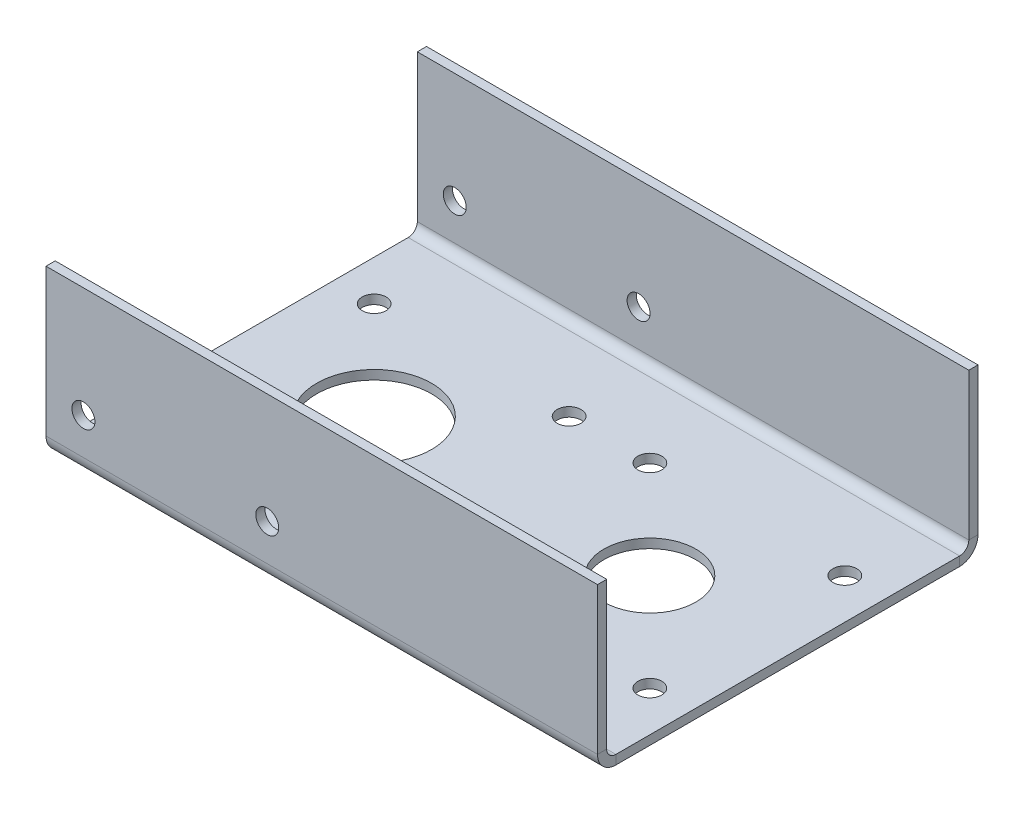
SolidWorks part; units mm, degrees
note: The reader was unsure of these and kept them because the rebuilt part matched: flange length of "Edge-Flange1".
ref_plane "Front Plane" through (0, 0, 0) normal (0, 0, 1) x (1, 0, 0)
ref_plane "Top Plane" through (0, 0, 0) normal (0, 1, 0) x (1, 0, 0)
ref_plane "Right Plane" through (0, 0, 0) normal (1, 0, 0) x (0, 0, -1)
sketch "Sketch1" plane through (0, 0, 0) normal (0, 1, 0) x (1, 0, 0)
  line L0 (-38.1, 25.019) -> (0, -25.019) construction
  line L1 (-38.1, 25.019) -> (38.1, 25.019)
  line L2 (-38.1, 25.019) -> (-38.1, -25.019)
  line L3 (-38.1, -25.019) -> (38.1, -25.019)
  line L4 (38.1, 25.019) -> (38.1, -25.019)
  line L5 (-38.1, 25.019) -> (38.1, -25.019) construction
  circle A0 centre (-19.05, 0) radius 7.9375
  point P0 (-19.05, 0)
  point P8 (0, 0)
  point P9 (-19.05, 0)
  dimension "D3" = 15.875
  dimension "D1" = 76.2
  dimension "D2" = 50.038
base flange "Base-Flange1" sketch "Sketch1" thickness 1.27 reverse thickness direction no parameters "D1"=1.27
edge flange "Edge-Flange1" sketch "Sketch8" flange angle 90 flange length 22.86 flange position material outside bend radius 1.27 thickness 1.27 relief rectangular parameters "D6"=10
sketch "Sketch8" plane through (0, 0, 25.019) normal (0, 0, 1) x (1, 0, 0)
  line L0 (-38.1, 0) -> (38.1, 0) construction
  line L1 (-38.1, 0) -> (38.1, 0)
  line L2 (-38.1, 0) -> (-38.1, 21.59)
  line L3 (-38.1, 21.59) -> (38.1, 21.59)
  line L4 (38.1, 21.59) -> (38.1, 0)
  dimension "D1" = 21.59
bend "EdgeBend1" bend radius 1.27 bend angle 90 parameters "D5"=1
mirror "Mirror1" about plane through (0, 0, 0) normal (0, 0, 1) of "Edge-Flange1"
bend "MirrorBend1" bend radius 1.27 bend angle 90 parameters "D5"=2
sketch "Sketch9" plane through (0, 0, 0) normal (0, 1, 0) x (1, 0, 0)
  line L2 (-19.05, 0) -> (-42.2675, 0) construction
  line L3 (-19.05, 0) -> (-32.5204, 13.4704) construction
  circle A3 centre (-32.5204, 13.4704) radius 1.651
  circle A5 centre (-19.05, 0) radius 19.05 construction
  dimension "D4" = 3.302
  dimension "D5" = 38.1
  dimension "D6" = 45
extrude "Cut-Extrude3" cut sketch "Sketch9" against normal through all contours A3 normal cut yes
pattern_circular "CirPattern2" count 4 over 360 about axis through (-19.05, 0, 0) along (0, 1, 0) of "Cut-Extrude3"
sketch "Sketch11" plane through (0, 0, 0) normal (0, 1, 0) x (1, 0, 0)
  line L0 (-19.05, 0) -> (19.05, 0) construction
  line L1 (19.05, 0) -> (5.5796, 13.4704) construction
  circle A0 centre (19.05, 0) radius 6.35
  circle A1 centre (19.05, 0) radius 19.05 construction
  circle A2 centre (5.5796, 13.4704) radius 1.651
  dimension "D1" = 12.7
  dimension "D2" = 38.1
  dimension "D4" = 3.302
  dimension "D3" = 38.1
  dimension "D5" = 45
extrude "Cut-Extrude4" cut sketch "Sketch11" against normal blind 2.54 normal cut yes
pattern_circular "CirPattern3" count 4 over 360 about axis through (19.05, 0, 0) along (0, 1, 0) of "Cut-Extrude4"
sketch "Sketch10" plane through (0, 0, -26.289) normal (0, 0, -1) x (-1, 0, 0)
  line L0 (-38.1, 6.35) -> (38.1, 6.35) construction
  line L1 (-38.1, 1.27) -> (-38.1, 21.59) construction
  line L2 (38.1, 21.59) -> (38.1, 1.27) construction
  line L5 (38.1, 1.27) -> (-38.1, 1.27) construction
  circle A0 centre (7.5286, 6.35) radius 1.5875
  circle A1 centre (32.9286, 6.35) radius 1.5875
  dimension "D1" = 3.175
  dimension "D2" = 25.4
  dimension "D4" = 5.1714
  dimension "D3" = 5.08
extrude "Cut-Extrude2" cut sketch "Sketch10" against normal through all both and the other way through all normal cut yes
sketch "Bend-Lines1" [suppressed] plane through (0, 0, 0) normal (0, 1, 0) x (1, 0, 0)
sketch "Bounding-Box1" [suppressed] plane through (0, 0, 0) normal (0, 1, 0) x (1, 0, 0)
sheet metal parameters "Sheet-Metal1" thickness 1.27 parameters "D1"=1.27
flat pattern "Flat-Pattern1" [suppressed]
sketch "Bend-Lines2" plane through (0, 0, 0) normal (0, 1, 0) x (1, 0, 0)
sketch3d "Bounding-Box2" [suppressed]
  line L0 (18.0975, 22.225, 0) -> (18.0975, -22.225, 0) construction
  line L1 (-18.0975, 22.225, 0) -> (-18.0975, -22.225, 0) construction
  line L2 (18.0975, 22.225, 0) -> (-18.0975, 22.225, 0) construction
  line L3 (18.0975, -22.225, 0) -> (-18.0975, -22.225, 0) construction
sheet metal parameters "Sheet-Metal2" thickness 1.27 parameters "D1"=1.27
flat pattern "Flat-Pattern1"
sketch "Bend-Lines2" plane through (0, 0, 0) normal (0, 1, 0) x (1, 0, 0)
  line L0 (-18.0975, -22.4512) -> (18.0975, -22.4512) construction
  line L1 (-18.0975, -22.4512) -> (18.0975, -22.4512) construction
sketch3d "Bounding-Box2" [suppressed]
  line L0 (-18.0975, 22.225, 0) -> (-18.0975, -34.1074, 0) construction
  line L1 (18.0975, 22.225, 0) -> (18.0975, -34.1074, 0) construction
  line L2 (-18.0975, 22.225, 0) -> (18.0975, 22.225, 0) construction
  line L3 (-18.0975, -34.1074, 0) -> (18.0975, -34.1074, 0) construction
bend of the flat pattern "Flatten-<EdgeBend1>1"
sheet metal parameters "Sheet-Metal3" thickness 1.27 parameters "D1"=1.27
flat pattern "Flat-Pattern1"
sketch "Bend-Lines2" plane through (0, 0, 0) normal (0, 1, 0) x (1, 0, 0)
  line L0 (-38.1, -25.2452) -> (38.1, -25.2452) construction
  line L1 (-38.1, -25.2452) -> (38.1, -25.2452) construction
  line L2 (38.1, 25.2452) -> (-38.1, 25.2452) construction
  line L3 (38.1, 25.2452) -> (-38.1, 25.2452) construction
sketch3d "Bounding-Box2" [suppressed]
  line L0 (38.1, -36.9014, 0) -> (-38.1, -36.9014, 0) construction
  line L1 (38.1, 36.9014, 0) -> (-38.1, 36.9014, 0) construction
  line L2 (38.1, -36.9014, 0) -> (38.1, 36.9014, 0) construction
  line L3 (-38.1, -36.9014, 0) -> (-38.1, 36.9014, 0) construction
bend of the flat pattern "Flatten-<EdgeBend1>1"
bend of the flat pattern "Flatten-<MirrorBend1>1"
sheet metal parameters "Sheet-Metal6" thickness 1.27 parameters "D1"=1.27
flat pattern "Flat-Pattern1"
sketch "Bend-Lines2" plane through (0, 0, 0) normal (0, 1, 0) x (1, 0, 0)
  line L0 (-38.1, -25.2452) -> (38.1, -25.2452) construction
  line L1 (-38.1, -25.2452) -> (38.1, -25.2452) construction
  line L2 (38.1, 25.2452) -> (-38.1, 25.2452) construction
  line L3 (38.1, 25.2452) -> (-38.1, 25.2452) construction
sketch3d "Bounding-Box2" [suppressed]
  line L0 (-38.1, 47.0614, 0) -> (-38.1, -47.0614, 0) construction
  line L1 (38.1, 47.0614, 0) -> (38.1, -47.0614, 0) construction
  line L2 (-38.1, 47.0614, 0) -> (38.1, 47.0614, 0) construction
  line L3 (-38.1, -47.0614, 0) -> (38.1, -47.0614, 0) construction
bend of the flat pattern "Flatten-<EdgeBend1>1"
bend of the flat pattern "Flatten-<MirrorBend1>1"
sheet metal parameters "Sheet-Metal9" thickness 1.27 parameters "D1"=1.27
flat pattern "Flat-Pattern1"
sketch "Bend-Lines2" plane through (0, 0, 0) normal (0, 1, 0) x (1, 0, 0)
  line L0 (-38.1, -25.2452) -> (38.1, -25.2452) construction
  line L1 (-38.1, -25.2452) -> (38.1, -25.2452) construction
  line L2 (38.1, 25.2452) -> (-38.1, 25.2452) construction
  line L3 (38.1, 25.2452) -> (-38.1, 25.2452) construction
sketch3d "Bounding-Box2" [suppressed]
  line L0 (38.1, -36.9014, 0) -> (-38.1, -36.9014, 0) construction
  line L1 (38.1, 36.9014, 0) -> (-38.1, 36.9014, 0) construction
  line L2 (38.1, -36.9014, 0) -> (38.1, 36.9014, 0) construction
  line L3 (-38.1, -36.9014, 0) -> (-38.1, 36.9014, 0) construction
bend of the flat pattern "Flatten-<EdgeBend1>1"
bend of the flat pattern "Flatten-<MirrorBend1>1"
sheet metal parameters "Sheet-Metal10" thickness 1.27 parameters "D1"=1.27
flat pattern "Flat-Pattern1"
sketch "Bend-Lines2" plane through (0, 0, 0) normal (0, 1, 0) x (1, 0, 0)
  line L0 (-38.1, -25.2452) -> (38.1, -25.2452) construction
  line L1 (-38.1, -25.2452) -> (38.1, -25.2452) construction
  line L2 (38.1, 25.2452) -> (-38.1, 25.2452) construction
  line L3 (38.1, 25.2452) -> (-38.1, 25.2452) construction
sketch3d "Bounding-Box2" [suppressed]
  line L0 (38.1, -36.9014, 0) -> (-38.1, -36.9014, 0) construction
  line L1 (38.1, 36.9014, 0) -> (-38.1, 36.9014, 0) construction
  line L2 (38.1, -36.9014, 0) -> (38.1, 36.9014, 0) construction
  line L3 (-38.1, -36.9014, 0) -> (-38.1, 36.9014, 0) construction
bend of the flat pattern "Flatten-<EdgeBend1>1"
bend of the flat pattern "Flatten-<MirrorBend1>1"
sheet metal parameters "Sheet-Metal11" thickness 1.27 parameters "D1"=1.27
flat pattern "Flat-Pattern1"
sketch "Bend-Lines2" plane through (0, 0, 0) normal (0, 1, 0) x (1, 0, 0)
  line L0 (-38.1, -25.2452) -> (38.1, -25.2452) construction
  line L1 (-38.1, -25.2452) -> (38.1, -25.2452) construction
  line L2 (38.1, 25.2452) -> (-38.1, 25.2452) construction
  line L3 (38.1, 25.2452) -> (-38.1, 25.2452) construction
sketch3d "Bounding-Box2" [suppressed]
  line L0 (38.1, -36.9014, 0) -> (-38.1, -36.9014, 0) construction
  line L1 (38.1, 36.9014, 0) -> (-38.1, 36.9014, 0) construction
  line L2 (38.1, -36.9014, 0) -> (38.1, 36.9014, 0) construction
  line L3 (-38.1, -36.9014, 0) -> (-38.1, 36.9014, 0) construction
bend of the flat pattern "Flatten-<EdgeBend1>1"
bend of the flat pattern "Flatten-<MirrorBend1>1"
sheet metal parameters "Sheet-Metal12" thickness 1.27 parameters "D1"=1.27
flat pattern "Flat-Pattern1"
sketch "Bend-Lines2" plane through (0, 0, 0) normal (0, 1, 0) x (1, 0, 0)
  line L0 (-38.1, -25.2452) -> (38.1, -25.2452) construction
  line L1 (-38.1, -25.2452) -> (38.1, -25.2452) construction
  line L2 (38.1, 25.2452) -> (-38.1, 25.2452) construction
  line L3 (38.1, 25.2452) -> (-38.1, 25.2452) construction
sketch3d "Bounding-Box2" [suppressed]
  line L0 (38.1, -36.9014, 0) -> (-38.1, -36.9014, 0) construction
  line L1 (38.1, 36.9014, 0) -> (-38.1, 36.9014, 0) construction
  line L2 (38.1, -36.9014, 0) -> (38.1, 36.9014, 0) construction
  line L3 (-38.1, -36.9014, 0) -> (-38.1, 36.9014, 0) construction
bend of the flat pattern "Flatten-<EdgeBend1>1"
bend of the flat pattern "Flatten-<MirrorBend1>1"
